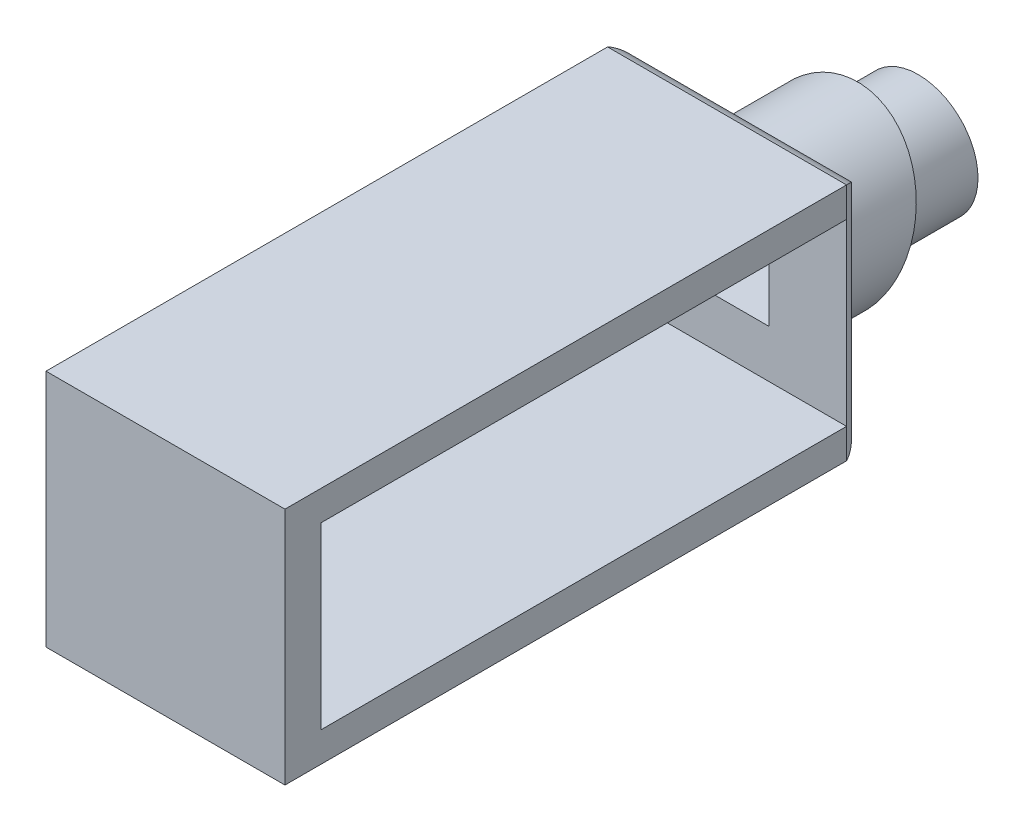
SolidWorks part; units mm, degrees
ref_plane "Alzado" through (0, 0, 0) normal (0, 0, 1) x (1, 0, 0)
ref_plane "Planta" through (0, 0, 0) normal (0, 1, 0) x (1, 0, 0)
ref_plane "Vista lateral" through (0, 0, 0) normal (1, 0, 0) x (0, 0, -1)
sketch "Croquis1" plane through (0, 0, 0) normal (0, 0, 1) x (1, 0, 0)
  circle A0 centre (0, 0) radius 2.5
  circle A1 centre (0, 0) radius 1.8
  dimension "D1" = 5
  dimension "D2" = 3.6
extrude "Saliente-Extruir1" add sketch "Croquis1" along normal blind 7
ref_axis "Eje1" through (2.75, 0, 7) along (-1, 0, 0)
ref_plane "Plano1" through (0, 2.2498, 6.1812) normal (0, -0.342, -0.9397) x (-1, 0, 0)
ref_plane "Plano3" through (0, 1.2237, 3.3621) normal (0, -0.342, -0.9397) x (-1, 0, 0)
sketch "Croquis3" plane through (0, 0, 7) normal (0, 0, 1) x (1, 0, 0)
  circle A0 centre (0, 0) radius 1.6
  circle A1 centre (0, 0) radius 3.5
  dimension "D1" = 7
extrude "Saliente-Extruir2" add sketch "Croquis3" against normal up to surface (3.1925 mm away) up to plane "Plano3"
sketch "Croquis4" plane through (0, 0, 7) normal (0, 0, 1) x (1, 0, 0)
  line L1 (5, -5) -> (-5, -5)
  line L2 (5, -5) -> (5, 5)
  line L3 (5, 5) -> (-5, 5)
  line L4 (-5, -5) -> (-5, 5)
  line L5 (5, -5) -> (-5, 5) construction
  line L6 (5, 5) -> (-5, -5) construction
  point P0 (0, 0)
  dimension "D1" = 10
  dimension "D2" = 10
extrude "Saliente-Extruir3" add sketch "Croquis4" along normal blind 1
fillet "Redondeo2" radius 1.5 4 edges at (-5, 0, 7) (0, -5, 7) (5, 0, 7) (0, 5, 7)
sketch "Croquis7" plane through (0, 0, 8) normal (0, 0, 1) x (1, 0, 0)
  line L1 (1.75, 1.75) -> (-1.75, 1.75)
  line L2 (1.75, 1.75) -> (1.75, -1.75)
  line L3 (1.75, -1.75) -> (-1.75, -1.75)
  line L4 (-1.75, 1.75) -> (-1.75, -1.75)
  line L5 (1.75, 1.75) -> (-1.75, -1.75) construction
  line L6 (1.75, -1.75) -> (-1.75, 1.75) construction
  point P0 (0, 0)
  dimension "D1" = 3.5
  dimension "D2" = 3.5
extrude "Cortar-Extruir1" cut sketch "Croquis7" against normal blind 3
sketch "Croquis8" plane through (0, 0, 8) normal (0, 0, 1) x (1, 0, 0)
  line L1 (3.75, 5) -> (-5, 5)
  line L3 (3.75, -5) -> (-5, -5)
  line L4 (-5, 5) -> (-5, -5)
  line L5 (5, 5) -> (-5, -5) construction
  line L6 (5, -5) -> (-5, 5) construction
  line L7 (3.75, 3.75) -> (-3.75, 3.75)
  line L9 (3.75, -3.75) -> (-3.75, -3.75)
  line L10 (-3.75, 3.75) -> (-3.75, -3.75)
  line L11 (3.75, 3.75) -> (-3.75, -3.75) construction
  line L12 (3.75, -3.75) -> (-3.75, 3.75) construction
  line L14 (3.75, 3.75) -> (5, 3.75)
  line L15 (5, -5) -> (5, 5) construction
  line L16 (5, 3.75) -> (5, 5)
  line L17 (5, 5) -> (3.75, 5)
  line L18 (3.75, -3.75) -> (5, -3.75)
  line L19 (5, -3.75) -> (5, -5)
  line L20 (5, -5) -> (3.75, -5)
  point P0 (0, 0)
  point P7 (0, 0)
  dimension "D1" = 7.5
extrude "Saliente-Extruir4" add sketch "Croquis8" along normal blind 22
sketch "Croquis9" plane through (0, 0, 30) normal (0, 0, 1) x (1, 0, 0)
  line L1 (5, 5) -> (-5, 5)
  line L2 (5, 5) -> (5, -5)
  line L3 (5, -5) -> (-5, -5)
  line L4 (-5, 5) -> (-5, -5)
  line L5 (5, 5) -> (-5, -5) construction
  line L6 (5, -5) -> (-5, 5) construction
  point P0 (0, 0)
extrude "Saliente-Extruir5" add sketch "Croquis9" along normal blind 1.5
